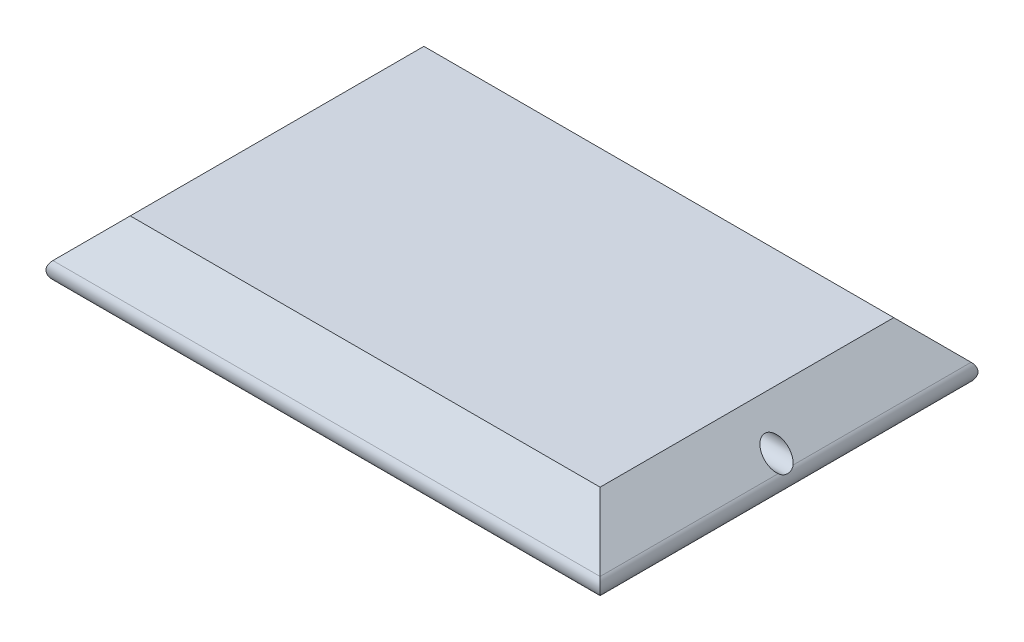
SolidWorks part; units mm, degrees
ref_plane "前视基准面" through (0, 0, 0) normal (0, 0, 1) x (1, 0, 0)
ref_plane "上视基准面" through (0, 0, 0) normal (0, 1, 0) x (1, 0, 0)
ref_plane "右视基准面" through (0, 0, 0) normal (1, 0, 0) x (0, 0, -1)
sketch "草图1" plane through (0, 0, 0) normal (0, 1, 0) x (1, 0, 0)
  line L1 (-50, 35) -> (50, 35)
  line L2 (-50, 35) -> (-50, -35)
  line L3 (-50, -35) -> (50, -35)
  line L4 (50, 35) -> (50, -35)
  line L5 (-50, 35) -> (50, -35) construction
  line L6 (-50, -35) -> (50, 35) construction
  point P0 (0, 0)
  dimension "D1" = 100
  dimension "D2" = 70
extrude "凸台-拉伸1" add sketch "草图1" along normal blind 10 draft 45
sketch "草图2" plane through (0, 0, 0) normal (0, 0, 1) x (1, 0, 0)
  line L0 (65.4142, 4.815) -> (-25.4721, 4.815)
  line L1 (28.8783, 6.815) -> (65.4142, 6.815)
  line L2 (65.4142, 4.815) -> (65.4142, 6.815)
  circle A0 centre (25.4142, 4.815) radius 4
  dimension "D2" = 8
  dimension "D1" = 2
  dimension "D3" = 40
revolve "切除-旋转2" cut sketch "草图2" angle 360 about L0 region at (25.4142, 6.5126, 0)
sketch "草图5" plane through (0, 0, 0) normal (0, 0, 1) x (1, 0, 0)
  line L1 (54.7999, 4.9615) -> (25.9261, 4.9615)
  line L2 (54.7999, 4.9615) -> (54.7999, 6.9615)
  line L3 (54.7999, 6.9615) -> (25.9261, 6.9615)
  line L4 (25.9261, 4.9615) -> (25.9261, 6.9615)
  dimension "D1" = 2
revolve "切除-旋转4" cut sketch "草图5" angle 360 about L1
fillet "圆角1" radius 2 4 edges at (-50, 0, 0) (0, 0, 35) (0, 0, -35) (50, 0, 0)
